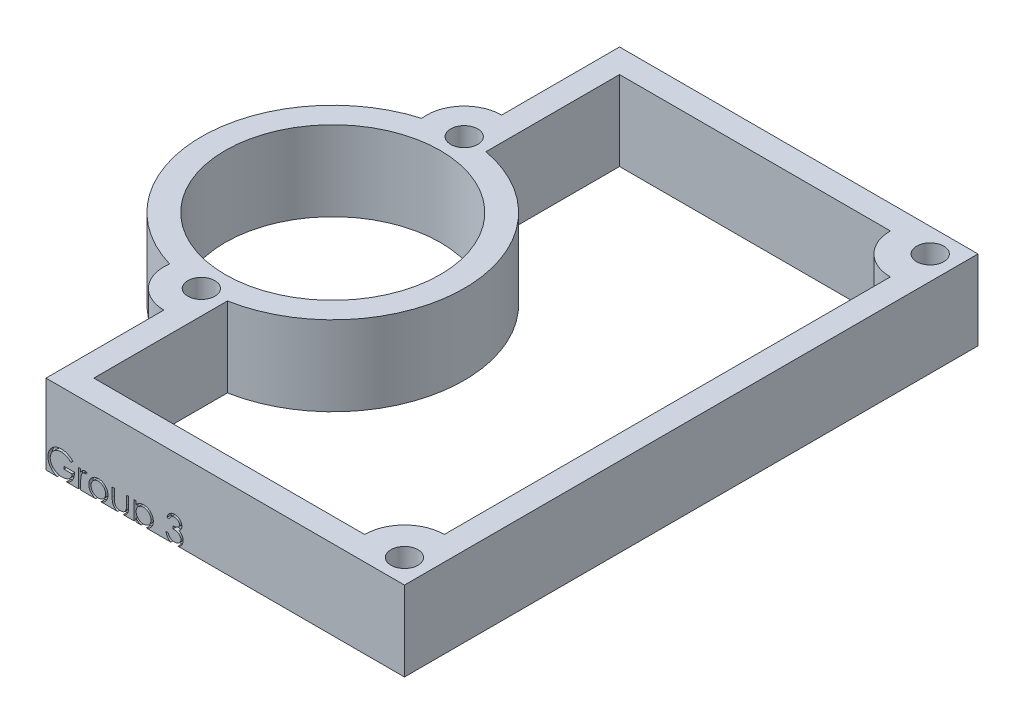
SolidWorks part; units mm, degrees
material "Acrylic (Medium-high impact)"
ref_plane "Front Plane" through (0, 0, 0) normal (0, 0, 1) x (1, 0, 0)
ref_plane "Top Plane" through (0, 0, 0) normal (0, 1, 0) x (1, 0, 0)
ref_plane "Right Plane" through (0, 0, 0) normal (1, 0, 0) x (0, 0, -1)
sketch "Sketch2" plane through (0, 0, 0) normal (0, 1, 0) x (1, 0, 0)
  line L0 (-55, 0) -> (55, 0) construction
  line L1 (0, 21.2) -> (0, 36)
  line L2 (0, 36) -> (45, 36)
  line L3 (45, -36) -> (45, 36)
  line L4 (0, -21.2) -> (0, -36)
  line L5 (0, -36) -> (45, -36)
  circle A0 centre (0, 0) radius 13.5
  arc A1 (-4.6521, 15.8306) -> (-4.6521, -15.8306) centre (0, 0) ccw
  arc A2 (-4.6521, 15.8306) -> (4.6521, 15.8306) centre (0, 16.5) cw
  circle A3 centre (0, 0) radius 16.5 construction
  arc A4 (-4.6521, -15.8306) -> (4.6521, -15.8306) centre (0, -16.5) ccw
  arc A5 (4.6521, -15.8306) -> (4.6521, 15.8306) centre (0, 0) ccw
  circle A6 centre (0, 16.5) radius 1.7
  circle A7 centre (0, -16.5) radius 1.7
  arc A8 (4.6521, 15.8306) -> (4.6521, -15.8306) centre (0, 0) ccw
  arc A9 (4.6521, 15.8306) -> (4.6521, -15.8306) centre (0, 0) cw
  arc A11 (4.6521, 15.8306) -> (4.6521, -15.8306) centre (0, 0) cw
  point P8 (45, 0)
  dimension "D1" = 27
  dimension "D2" = 3
  dimension "D3" = 3.4
  dimension "D4" = 3
  dimension "D5" = 72
  dimension "D6" = 45
extrude "Boss-Extrude2" add sketch "Sketch2" along normal blind 10 contours A8 A2 A6 | A7 A8 A5 A6 A1 A0 | A8 A7 A4 | A5 A4 L4 L5 L3 L2 L1 A2 region at (0, 0, -18.5372) region at (25.1585, 0, 0) region at (-3.0983, 0, -15.7324) region at (0, 0, 18.5372)
sketch "Sketch3" plane through (0, 10, 0) normal (0, 1, 0) x (1, 0, 0)
  line L0 (3, 16.225) -> (3, 33)
  line L1 (3, 33) -> (42, 33)
  line L2 (42, 33) -> (42, -33)
  line L3 (42, -33) -> (3, -33)
  line L4 (3, -33) -> (3, -16.225)
  line L5 (0, 21.2) -> (0, 36) construction
  line L6 (0, 36) -> (45, 36) construction
  line L7 (45, -36) -> (45, 36) construction
  line L8 (0, -36) -> (45, -36) construction
  line L9 (0, -21.2) -> (0, -36) construction
  circle A0 centre (0, 0) radius 16.5 construction
  arc A1 (-4.6521, 15.8306) -> (-4.6521, -15.8306) centre (0, 0) ccw construction
  arc A2 (3, 16.225) -> (3, -16.225) centre (0, 0) cw
  dimension "D1" = 3
  dimension "D2" = 3
  dimension "D3" = 3
  dimension "D4" = 3
  dimension "D5" = 3
extrude "Cut-Extrude1" cut sketch "Sketch3" against normal through all
sketch "Sketch4" plane through (0, 10, 0) normal (0, 1, 0) x (1, 0, 0)
  line L1 (42, 33) -> (3, 33) construction
  line L2 (42, -33) -> (42, 33) construction
  line L3 (3, -33) -> (42, -33) construction
  line L4 (37, -33) -> (42, -33)
  line L5 (42, -33) -> (42, -28)
  line L6 (37, 33) -> (42, 33)
  line L7 (42, 33) -> (42, 28)
  arc A0 (37, 33) -> (42, 28) centre (42, 33) ccw
  arc A1 (37, -33) -> (42, -28) centre (42, -33) cw
  dimension "D1" = 5
  dimension "D2" = 5
extrude "Boss-Extrude3" add sketch "Sketch4" against normal through all
sketch "Sketch5" plane through (0, 10, 0) normal (0, 1, 0) x (1, 0, 0)
  circle A0 centre (42, 33) radius 1.7
  circle A1 centre (42, -33) radius 1.7
  arc A2 (42, -28) -> (37, -33) centre (42, -33) ccw construction
  arc A3 (37, 33) -> (42, 28) centre (42, 33) ccw construction
  dimension "D1" = 3.4
  dimension "D2" = 3.4
extrude "Cut-Extrude3" cut sketch "Sketch5" against normal through all
sketch "Sketch6" plane through (0, 0, 36) normal (0, 0, 1) x (1, 0, 0)
  text T0 "Group 3"
extrude "Cut-Extrude4" cut sketch "Sketch6" against normal blind 0.5
